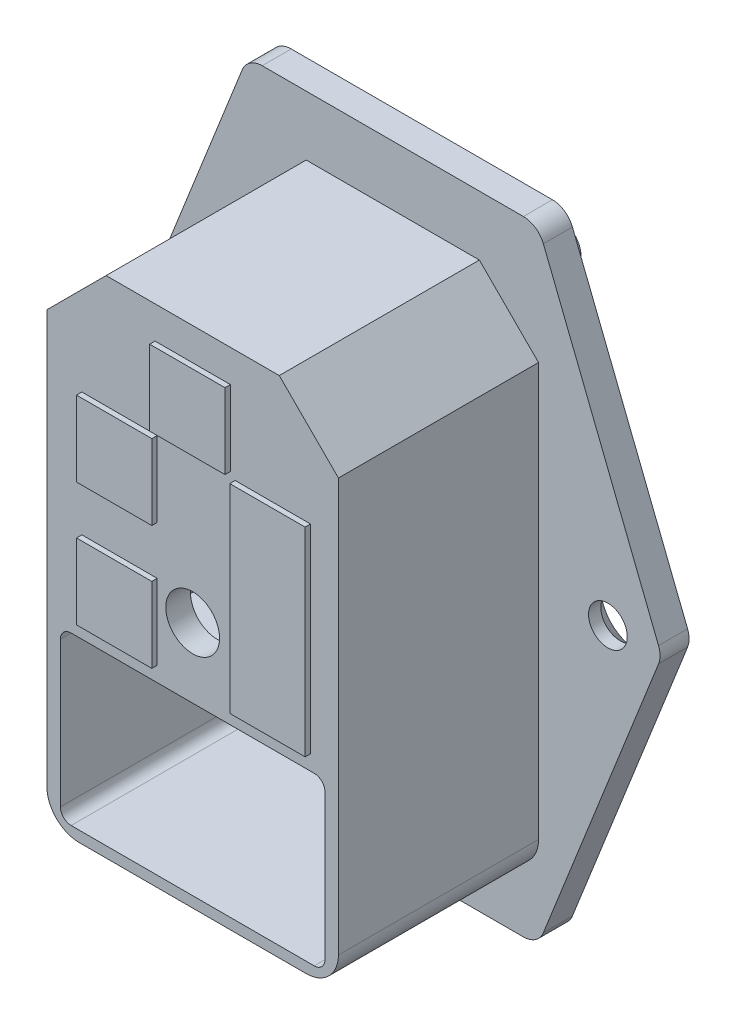
SolidWorks part; units mm, degrees
ref_plane "Front Plane" through (0, 0, 0) normal (0, 0, 1) x (1, 0, 0)
ref_plane "Top Plane" through (0, 0, 0) normal (0, 1, 0) x (1, 0, 0)
ref_plane "Right Plane" through (0, 0, 0) normal (1, 0, 0) x (0, 0, -1)
sketch "Sketch1" plane through (0, 0, 0) normal (0, 0, 1) x (1, 0, 0)
  line L0 (-13.5, 29) -> (-25, 0)
  line L1 (-13.5, -29) -> (13.5, -29)
  line L2 (-13.5, -29) -> (-13.5, 29)
  line L3 (-13.5, 29) -> (13.5, 29)
  line L4 (13.5, -29) -> (13.5, 29)
  line L5 (-13.5, -29) -> (13.5, 29) construction
  line L6 (-13.5, 29) -> (13.5, -29) construction
  line L7 (-25, 0) -> (-13.5, -29)
  line L8 (-25, 0) -> (25, 0) construction
  line L9 (-25, 0) -> (-13.5, 29)
  line L10 (-13.5, -29) -> (-25, 0)
  line L11 (0, 29) -> (0, -29) construction
  line L12 (-25, 0) -> (-13.5, 29)
  line L13 (-13.5, -29) -> (-25, 0)
  line L14 (25, 0) -> (13.5, -29)
  line L15 (13.5, 29) -> (25, 0)
  point P0 (0, 0)
  point P11 (0, 0)
  dimension "D1" = 58
  dimension "D2" = 27
  dimension "D3" = 50
extrude "Boss-Extrude1" add sketch "Sketch1" along normal blind 2.7 contours L0 L7 L2 | L1 L4 L3 L2 | L15 L4 L14 region at (-17.3333, 0, 0) region at (0, 0, 0) region at (17.3333, 0, 0)
fillet "Fillet1" radius 2 6 edges at (-25, 0, 1.35) (-13.5, 29, 1.35) (-13.5, -29, 1.35) (13.5, -29, 1.35) (25, 0, 1.35) (13.5, 29, 1.35)
sketch "Sketch2" plane through (0, 0, 0) normal (0, 0, -1) x (-1, 0, 0)
  line L1 (-12.1, -27.1) -> (12.1, -27.1)
  line L2 (-14.1, -25.1) -> (-14.1, 25.1)
  line L3 (-12.1, 27.1) -> (12.1, 27.1)
  line L4 (14.1, -25.1) -> (14.1, 25.1)
  line L5 (-14.1, -27.1) -> (14.1, 27.1) construction
  line L6 (-14.1, 27.1) -> (14.1, -27.1) construction
  arc A0 (12.1, -27.1) -> (14.1, -25.1) centre (12.1, -25.1) ccw
  arc A1 (-12.1, -27.1) -> (-14.1, -25.1) centre (-12.1, -25.1) cw
  arc A2 (12.1, 27.1) -> (14.1, 25.1) centre (12.1, 25.1) cw
  arc A3 (-14.1, 25.1) -> (-12.1, 27.1) centre (-12.1, 25.1) cw
  point P0 (0, 0)
  dimension "D3" = 2
  dimension "D1" = 54.2
  dimension "D2" = 28.2
extrude "Boss-Extrude2" add sketch "Sketch2" along normal blind 0.7
sketch "Sketch3" plane through (0, 0, 2.7) normal (0, 0, 1) x (1, 0, 0)
  line L0 (-20, 0) -> (20, 0) construction
  line L1 (-11, -24) -> (11, -24)
  line L2 (-14, -21) -> (-14, 21)
  line L3 (-11, 24) -> (11, 24)
  line L4 (14, -21) -> (14, 21)
  line L5 (-14, -24) -> (14, 24) construction
  line L6 (-14, 24) -> (14, -24) construction
  circle A0 centre (-20, 0) radius 2.25
  circle A1 centre (20, 0) radius 2.25
  arc A2 (-11, -24) -> (-14, -21) centre (-11, -21) cw
  arc A3 (11, -24) -> (14, -21) centre (11, -21) ccw
  arc A4 (11, 24) -> (14, 21) centre (11, 21) cw
  arc A5 (-14, 21) -> (-11, 24) centre (-11, 21) cw
  point P0 (0, 0)
  point P9 (0, 0)
  dimension "D4" = 4.5
  dimension "D5" = 3
  dimension "D1" = 28
  dimension "D2" = 48
  dimension "D3" = 40
sketch "Sketch5" plane through (0, 0, 2.7) normal (0, 0, 1) x (1, 0, 0)
  line L1 (-13.55, -23.45) -> (13.55, -23.45)
  line L2 (-13.55, -23.45) -> (-13.55, 23.45)
  line L3 (-13.55, 23.45) -> (13.55, 23.45)
  line L4 (13.55, -23.45) -> (13.55, 23.45)
  line L5 (-13.55, -23.45) -> (13.55, 23.45) construction
  line L6 (-13.55, 23.45) -> (13.55, -23.45) construction
  point P0 (0, 0)
  dimension "D1" = 46.9
  dimension "D2" = 27.1
extrude "Boss-Extrude3" add sketch "Sketch5" along normal blind 18.6
fillet "Fillet2" radius 3 2 edges at (-13.55, -23.45, 12) (13.55, -23.45, 12)
chamfer "Chamfer1" distance 5.5 angle 45 2 edges at (13.55, 23.45, 12) (-13.55, 23.45, 12)
sketch "Sketch6" plane through (0, 0, 21.3) normal (0, 0, 1) x (1, 0, 0)
  line L0 (0, 0) -> (0, -14.7) construction
  line L1 (-11.3, -22.45) -> (11.3, -22.45)
  line L2 (-12.3, -21.45) -> (-12.3, -7.95)
  line L3 (-11.3, -6.95) -> (11.3, -6.95)
  line L4 (12.3, -21.45) -> (12.3, -7.95)
  line L5 (-12.3, -22.45) -> (12.3, -6.95) construction
  line L6 (-12.3, -6.95) -> (12.3, -22.45) construction
  line L7 (-10.55, -23.45) -> (10.55, -23.45) construction
  arc A0 (-11.3, -22.45) -> (-12.3, -21.45) centre (-11.3, -21.45) cw
  arc A1 (11.3, -22.45) -> (12.3, -21.45) centre (11.3, -21.45) ccw
  arc A2 (11.3, -6.95) -> (12.3, -7.95) centre (11.3, -7.95) cw
  arc A3 (-12.3, -7.95) -> (-11.3, -6.95) centre (-11.3, -7.95) cw
  point P0 (0, -14.7)
  dimension "D3" = 1
  dimension "D1" = 15.5
  dimension "D2" = 24.6
  dimension "D4" = 1
extrude "Cut-Extrude1" cut sketch "Sketch6" against normal blind 15.8
sketch "Sketch7" plane through (0, 0, -0.7) normal (0, 0, -1) x (-1, 0, 0)
  line L0 (0, 14.4) -> (0, 0) construction
  line L1 (-12.45, 6.25) -> (12.45, 6.25)
  line L2 (-12.45, 6.25) -> (-12.45, 17.55)
  line L3 (-7.45, 22.55) -> (7.45, 22.55)
  line L4 (12.45, 6.25) -> (12.45, 17.55)
  line L5 (-12.45, 6.25) -> (12.45, 22.55) construction
  line L6 (-12.45, 22.55) -> (12.45, 6.25) construction
  line L7 (12.1, 27.1) -> (-12.1, 27.1) construction
  line L8 (-4.625, 3.8) -> (4.625, 3.8)
  line L9 (-4.625, 3.8) -> (-4.625, 6.25)
  line L10 (-4.625, 6.25) -> (4.625, 6.25)
  line L11 (4.625, 3.8) -> (4.625, 6.25)
  line L12 (-4.625, 3.8) -> (4.625, 6.25) construction
  line L13 (-4.625, 6.25) -> (4.625, 3.8) construction
  line L14 (-12.3, 3.8) -> (12.3, 3.8)
  line L15 (-12.3, 3.8) -> (-12.3, -4.75)
  line L16 (-12.3, -4.75) -> (12.3, -4.75)
  line L17 (12.3, 3.8) -> (12.3, -4.75)
  line L18 (-12.3, 3.8) -> (12.3, -4.75) construction
  line L19 (-12.3, -4.75) -> (12.3, 3.8) construction
  line L20 (12.1416, 29) -> (-12.1416, 29) construction
  line L21 (-12.45, 17.55) -> (-7.45, 22.55)
  line L22 (7.45, 22.55) -> (12.45, 17.55)
  point P0 (0, 14.4)
  point P8 (0, 5.025)
  point P13 (0, -0.475)
  dimension "D1" = 24.9
  dimension "D2" = 4.55
  dimension "D3" = 16.3
  dimension "D4" = 9.25
  dimension "D5" = 25.2
  dimension "D6" = 27.3
  dimension "D7" = 24.6
extrude "Cut-Extrude2" cut sketch "Sketch7" against normal blind 19.7 contours L1 L4 L3 L2 | L8 L11 L1 L9 | L17 L14 L8 L15 L16 region at (0, 13.9744, -0.7) region at (0, 5.025, -0.7) region at (0, -0.475, -0.7)
sketch "Sketch8" plane through (0, 0, 19) normal (0, 0, -1) x (-1, 0, 0)
  line L0 (-4.625, 5.025) -> (4.625, 5.025) construction
  line L1 (-4.625, 3.8) -> (-4.625, 6.25) construction
  line L2 (4.625, 3.8) -> (4.625, 6.25) construction
  line L4 (-12.3, -0.475) -> (12.3, -0.475) construction
  line L5 (-12.3, 3.8) -> (-12.3, -4.75) construction
  line L6 (12.3, 3.8) -> (12.3, -4.75) construction
  circle A0 centre (0, -0.475) radius 2.5
  dimension "D1" = 5
extrude "Cut-Extrude3" cut sketch "Sketch8" against normal through all
sketch "Sketch9" plane through (0, 0, -0.7) normal (0, 0, -1) x (-1, 0, 0)
  line L0 (0, -14.7) -> (0, 0) construction
  line L1 (-10, -21.2) -> (10, -21.2)
  line L2 (-10, -21.2) -> (-10, -8.2)
  line L3 (-10, -8.2) -> (10, -8.2)
  line L4 (10, -21.2) -> (10, -8.2)
  line L5 (-10, -21.2) -> (10, -8.2) construction
  line L6 (-10, -8.2) -> (10, -21.2) construction
  line L7 (-12.3, -14.7) -> (12.3, -14.7) construction
  line L11 (-11.3, -22.45) -> (11.3, -22.45)
  line L12 (-12.3, -7.95) -> (-12.3, -21.45)
  line L13 (11.3, -6.95) -> (-11.3, -6.95)
  line L14 (12.3, -21.45) -> (12.3, -7.95)
  line L15 (-11.3, -22.45) -> (11.3, -22.45) construction
  line L16 (-12.3, -7.95) -> (-12.3, -21.45) construction
  line L17 (11.3, -6.95) -> (-11.3, -6.95) construction
  line L18 (12.3, -21.45) -> (12.3, -7.95) construction
  arc A4 (11.3, -22.45) -> (12.3, -21.45) centre (11.3, -21.45) ccw
  arc A5 (-12.3, -21.45) -> (-11.3, -22.45) centre (-11.3, -21.45) ccw
  arc A6 (-11.3, -6.95) -> (-12.3, -7.95) centre (-11.3, -7.95) ccw
  arc A7 (12.3, -7.95) -> (11.3, -6.95) centre (11.3, -7.95) ccw
  arc A8 (11.3, -22.45) -> (12.3, -21.45) centre (11.3, -21.45) ccw construction
  arc A9 (-12.3, -21.45) -> (-11.3, -22.45) centre (-11.3, -21.45) ccw construction
  arc A10 (-11.3, -6.95) -> (-12.3, -7.95) centre (-11.3, -7.95) ccw construction
  arc A11 (12.3, -7.95) -> (11.3, -6.95) centre (11.3, -7.95) ccw construction
  point P0 (0, -14.7)
  dimension "D1" = 13
  dimension "D2" = 20
  dimension "D3" = 0
extrude "Cut-Extrude4" cut sketch "Sketch9" against normal through all contours L2 L1 L4 L3
sketch "Sketch10" plane through (0, 0, -0.7) normal (0, 0, -1) x (-1, 0, 0)
  line L0 (-10, -14.7) -> (10, -14.7) construction
  line L1 (-9.75, -22.45) -> (9.75, -22.45)
  line L2 (-10.75, -21.45) -> (-10.75, -7.95)
  line L3 (-9.75, -6.95) -> (9.75, -6.95)
  line L4 (10.75, -21.45) -> (10.75, -7.95)
  line L5 (-10.75, -22.45) -> (10.75, -6.95) construction
  line L6 (-10.75, -6.95) -> (10.75, -22.45) construction
  line L7 (-10, -21.2) -> (-10, -8.2) construction
  line L8 (10, -21.2) -> (10, -8.2) construction
  arc A0 (-9.75, -22.45) -> (-10.75, -21.45) centre (-9.75, -21.45) cw
  arc A1 (9.75, -22.45) -> (10.75, -21.45) centre (9.75, -21.45) ccw
  arc A2 (9.75, -6.95) -> (10.75, -7.95) centre (9.75, -7.95) cw
  arc A3 (-10.75, -7.95) -> (-9.75, -6.95) centre (-9.75, -7.95) cw
  point P0 (0, -14.7)
  dimension "D3" = 1
  dimension "D1" = 15.5
  dimension "D2" = 21.5
extrude "Cut-Extrude5" cut sketch "Sketch10" against normal blind 1.9
sketch "Sketch11" plane through (0, 0, 21.3) normal (0, 0, 1) x (1, 0, 0)
  line L0 (0, 16.95) -> (0, 0) construction
  line L1 (-3.5, 13.45) -> (3.5, 13.45)
  line L2 (-3.5, 13.45) -> (-3.5, 20.45)
  line L3 (-3.5, 20.45) -> (3.5, 20.45)
  line L4 (3.5, 13.45) -> (3.5, 20.45)
  line L5 (-3.5, 13.45) -> (3.5, 20.45) construction
  line L6 (-3.5, 20.45) -> (3.5, 13.45) construction
  line L7 (3.95, -5.55) -> (10.95, -5.55)
  line L8 (3.95, -5.55) -> (3.95, 12.95)
  line L9 (3.95, 12.95) -> (10.95, 12.95)
  line L10 (10.95, -5.55) -> (10.95, 12.95)
  line L11 (3.95, -5.55) -> (10.95, 12.95) construction
  line L12 (3.95, 12.95) -> (10.95, -5.55) construction
  line L13 (-10.3, 5.95) -> (-3.3, 5.95)
  line L14 (-10.3, 5.95) -> (-10.3, 12.95)
  line L15 (-10.3, 12.95) -> (-3.3, 12.95)
  line L16 (-3.3, 5.95) -> (-3.3, 12.95)
  line L17 (-10.3, 5.95) -> (-3.3, 12.95) construction
  line L18 (-10.3, 12.95) -> (-3.3, 5.95) construction
  line L19 (-10.3, -5.55) -> (-3.3, -5.55)
  line L20 (-10.3, -5.55) -> (-10.3, 1.45)
  line L21 (-10.3, 1.45) -> (-3.3, 1.45)
  line L22 (-3.3, -5.55) -> (-3.3, 1.45)
  line L23 (-10.3, -5.55) -> (-3.3, 1.45) construction
  line L24 (-10.3, 1.45) -> (-3.3, -5.55) construction
  line L25 (-6.8, 9.45) -> (-6.8, -2.05) construction
  line L26 (-13.55, 17.95) -> (-13.55, -20.45) construction
  line L27 (8.05, 23.45) -> (-8.05, 23.45) construction
  point P0 (0, 16.95)
  point P5 (7.45, 3.7)
  point P10 (-6.8, 9.45)
  point P15 (-6.8, -2.05)
  dimension "D1" = 7
  dimension "D2" = 18.5
  dimension "D3" = 3.25
  dimension "D4" = 7
  dimension "D5" = 22
  dimension "D6" = 17.5
  dimension "D7" = 10
extrude "Boss-Extrude4" add sketch "Sketch11" along normal blind 0.5
sketch "Sketch12" plane through (0, 0, 19) normal (0, 0, -1) x (-1, 0, 0)
  line L0 (-12.3, -0.475) -> (12.3, -0.475) construction
  line L1 (-10.9, -3.625) -> (-5.6, -3.625)
  line L2 (-10.9, -3.625) -> (-10.9, 2.675)
  line L3 (-10.9, 2.675) -> (-5.6, 2.675)
  line L4 (-5.6, -3.625) -> (-5.6, 2.675)
  line L5 (-10.9, -3.625) -> (-5.6, 2.675) construction
  line L6 (-10.9, 2.675) -> (-5.6, -3.625) construction
  line L7 (-12.3, 3.8) -> (-12.3, -4.75) construction
  line L8 (12.3, 3.8) -> (12.3, -4.75) construction
  line L13 (0, 22.55) -> (0, -0.475) construction
  line L14 (-7.45, 22.55) -> (7.45, 22.55) construction
  line L15 (10.9, 2.675) -> (5.6, 2.675)
  line L16 (5.6, -3.625) -> (5.6, 2.675)
  line L17 (10.9, -3.625) -> (5.6, -3.625)
  line L18 (10.9, -3.625) -> (10.9, 2.675)
  line L19 (6, 10.4) -> (6, 14.4)
  line L20 (-10.9, -2.175) -> (-5.6, -2.175)
  line L21 (-10.9, -2.175) -> (-10.9, 1.225)
  line L22 (-10.9, 1.225) -> (-5.6, 1.225)
  line L23 (-5.6, -2.175) -> (-5.6, 1.225)
  line L24 (-10.9, -2.175) -> (-5.6, 1.225) construction
  line L25 (-10.9, 1.225) -> (-5.6, -2.175) construction
  line L26 (5.6, -2.175) -> (10.9, -2.175)
  line L27 (5.6, -2.175) -> (5.6, 1.225)
  line L28 (5.6, 1.225) -> (10.9, 1.225)
  line L29 (10.9, -2.175) -> (10.9, 1.225)
  line L30 (5.6, -2.175) -> (10.9, 1.225) construction
  line L31 (5.6, 1.225) -> (10.9, -2.175) construction
  line L32 (-1, 14.15) -> (1, 14.15)
  line L33 (-1, 14.15) -> (-1, 18.15)
  line L34 (-1, 18.15) -> (1, 18.15)
  line L35 (1, 14.15) -> (1, 18.15)
  line L36 (-1, 14.15) -> (1, 18.15) construction
  line L37 (-1, 18.15) -> (1, 14.15) construction
  line L38 (-8, 10.4) -> (-6, 10.4)
  line L39 (-8, 10.4) -> (-8, 14.4)
  line L40 (-8, 14.4) -> (-6, 14.4)
  line L41 (-6, 10.4) -> (-6, 14.4)
  line L42 (-8, 10.4) -> (-6, 14.4) construction
  line L43 (-8, 14.4) -> (-6, 10.4) construction
  line L44 (6, 10.4) -> (8, 10.4)
  line L45 (8, 10.4) -> (8, 14.4)
  line L46 (6, 14.4) -> (8, 14.4)
  line L47 (-6, 12.4) -> (6, 12.4) construction
  line L48 (-7.45, 22.55) -> (7.45, 22.55) construction
  point P0 (-8.25, -0.475)
  point P15 (8.25, -0.475)
  point P20 (-8.25, -0.475)
  point P29 (-7, 12.4)
  point P30 (0, 16.15)
  point P45 (0, 12.4)
  dimension "D1" = 6.3
  dimension "D2" = 5.3
  dimension "D3" = 11.2
  dimension "D4" = 3.4
  dimension "D5" = 3.4
  dimension "D6" = 2
  dimension "D7" = 4
  dimension "D8" = 2
  dimension "D9" = 4
  dimension "D11" = 12
  dimension "D12" = 4.4
  dimension "D13" = 8.15
  dimension "D10" = 2
extrude "Boss-Extrude5" add sketch "Sketch12" along normal blind 9.9 contours L2 L22 L4 L3 | L20 L2 L1 L4 | L16 L28 L18 L15 | L26 L16 L17 L18 region at (8.25, -2.9, 19) region at (8.25, 1.95, 19) region at (-8.25, 1.95, 19) region at (-8.25, -2.9, 19)
extrude "Boss-Extrude6" add sketch "Sketch12<3>" along normal blind 14.6 contours L38 L41 L40 L39 | L46 L19 L44 L45 region at (-7, 12.4, 19) region at (7, 12.4, 19)
sketch "Sketch12<3>" plane through (0, 0, 19) normal (0, 0, -1) x (-1, 0, 0) same geometry as "Sketch12"
extrude "Boss-Extrude7" add sketch "Sketch12<4>" along normal blind 17.5 contours L32 L35 L34 L33 region at (0, 16.15, 19)
sketch "Sketch12<4>" plane through (0, 0, 19) normal (0, 0, -1) x (-1, 0, 0) same geometry as "Sketch12"
hole_wizard "CSK for M3 SFHCS1" positions "Sketch15" profile "Sketch16" countersink size "M3" standard "ANSI Metric" end condition up to next
sketch "Sketch15" plane through (0, 0, 0) normal (0, 0, -1) x (-1, 0, 0)
  point P0 (-20, 0)
  point P3 (20, 0)
sketch "Sketch16" plane through (20, 0, 0) normal (1, 0, 0) x (0, 1, 0)
  line L0 (0, 0) -> (0, 2.7)
  line L1 (0, 2.7) -> (1.8, 2.7)
  line L2 (1.8, 2.7) -> (1.8, 1.56)
  line L3 (1.8, 1.56) -> (3.36, 0)
  line L5 (3.36, 0) -> (0, 0)
  line L6 (-1.8, 1.56) -> (-3.36, 0) construction
  line L11 (0, -6.35) -> (0, 107.95) construction
  dimension "Thru Hole Dia." = 3.6
  dimension "Thru Hole Depth" = 2.7
  dimension "Near C'Sink Dia." = 6.72
  dimension "Near C'Sink Angle" = 90
